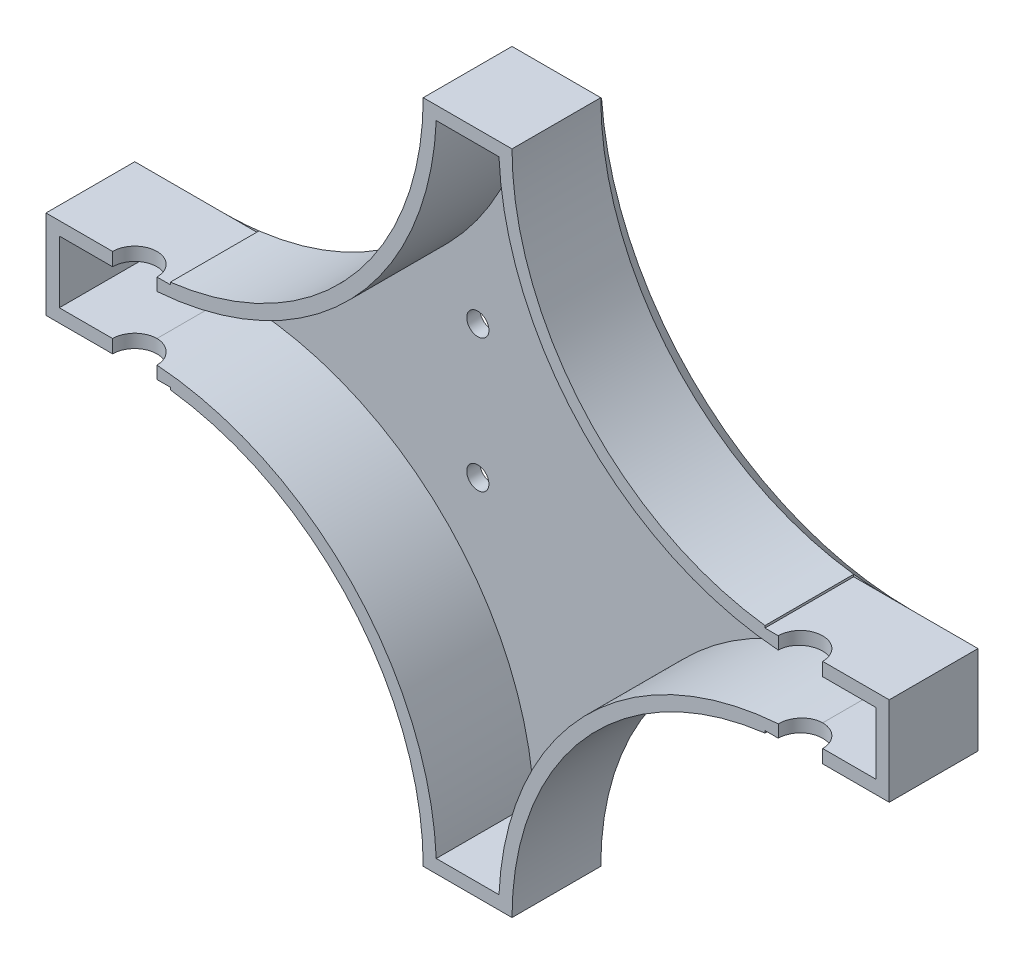
SolidWorks part; units mm, degrees
ref_plane "Front Plane" through (0, 0, 0) normal (0, 0, 1) x (1, 0, 0)
ref_plane "Top Plane" through (0, 0, 0) normal (0, 1, 0) x (1, 0, 0)
ref_plane "Right Plane" through (0, 0, 0) normal (1, 0, 0) x (0, 0, -1)
sketch "Sketch1" plane through (0, 0, 0) normal (0, 0, 1) x (1, 0, 0)
  line L1 (100, -75) -> (-100, -75)
  line L2 (100, -75) -> (100, 75)
  line L3 (100, 75) -> (-100, 75)
  line L4 (-100, -75) -> (-100, 75)
  line L5 (100, -75) -> (-100, 75) construction
  line L6 (100, 75) -> (-100, -75) construction
  point P0 (0, 0)
  dimension "D1" = 150
  dimension "D2" = 200
extrude "Boss-Extrude1" add sketch "Sketch1" along normal blind 25
sketch "Sketch2" plane through (0, 0, 0) normal (0, 0, -1) x (-1, 0, 0)
  line L0 (-100, 0) -> (100, 0)
  line L1 (0, 112.9215) -> (0, -139.2829) construction
  line L4 (-100, -75) -> (-100, 75) construction
  line L5 (100, 75) -> (100, -75) construction
sketch "Sketch5" plane through (0, 0, 0) normal (0, 0, -1) x (-1, 0, 0)
  line L0 (-100, 10) -> (106.2721, 10)
  line L1 (-100, -75) -> (-100, 75) construction
  line L2 (-15, -75) -> (5, -75)
  line L3 (-15, 75) -> (-15, -75)
  line L4 (-100, 0) -> (100, 0)
  line L5 (0, 10) -> (0, -10)
  line L6 (-65, -10) -> (101.6807, -10)
  line L7 (-65, -10) -> (-100, -10)
  line L8 (100, 75) -> (100, -75) construction
  line L9 (-100, 75) -> (100, 75) construction
  line L10 (100, -75) -> (-100, -75) construction
  line L11 (0, 112.9215) -> (0, -139.2829) construction
  line L12 (-15, 75) -> (5, 75)
  arc A3 (-80, 10) -> (-15, 75) centre (-80, 75) ccw
  arc A4 (-80, -10) -> (-15, -75) centre (-80, -75) cw
  arc A5 (5, 75) -> (70, 10) centre (70, 75) ccw
  arc A6 (5, -75) -> (70, -10) centre (70, -75) cw
  point P32 (70, -75)
  point P35 (70, -75)
  line M4 (100, -75) -> (100, 75)
  line M5 (100, 75) -> (-100, 75)
  line M6 (-100, 75) -> (-100, -75)
  line M7 (-100, -75) -> (100, -75)
  dimension "D2" = 15
  dimension "D3" = 130
  dimension "D4" = 130
  dimension "D5" = 100
  dimension "D6" = 85
extrude "Cut-Extrude2" cut sketch "Sketch5" against normal blind 30 contours A5 L0 M5 M4 | A6 L6 M7 M4 | A4 L7 M6 M7 | L0 A3 M5 M6 region at (62.9934, 46.0302, 0) region at (62.9934, -46.0302, 0) region at (-58.1762, 45.5946, 0) region at (-58.1762, -45.5946, 0)
shell "Shell2" thickness 3 removed face at (3.3333, 0, 25)
sketch "Sketch6" plane through (0, 0, 0) normal (0, 0, -1) x (-1, 0, 0)
  line L0 (-15, 75) -> (5, 75) construction
  line L1 (5, -75) -> (-15, -75) construction
  circle A0 centre (-5, 65) radius 2.5
  circle A1 centre (-5, -65) radius 2.5
  dimension "D1" = 5
  dimension "D2" = 5
  dimension "D3" = 10
  dimension "D4" = 10
extrude "Cut-Extrude3" cut sketch "Sketch6" against normal blind 30
sketch "Sketch7" plane through (0, 0, 0) normal (0, 1, 0) x (1, 0, 0)
  line L0 (-70, -25) -> (-100, -25) construction
  circle A0 centre (-80, -25) radius 5
  circle A1 centre (80, -25) radius 5
  dimension "D1" = 10
  dimension "D2" = 10
  dimension "D3" = 20
  dimension "D4" = 20
extrude "Cut-Extrude4" cut sketch "Sketch7" against normal blind 30 and the other way blind 30
chamfer "Chamfer1" distance 5 angle 45 12 edges at (-24.0381, 29.0381, 0) (-85, 10, 0) (-100, 0, 0) (-85, -10, 0) (90, -10, 0) (-24.0381, -29.0381, 0) (5, -75, 0) (34.0381, -29.0381, 0) (100, 0, 0) (5, 75, 0) (34.0381, 29.0381, 0) (90, 10, 0)
sketch "Sketch8" plane through (0, 0, 3) normal (0, 0, 1) x (1, 0, 0)
  line L0 (-24.8165, 0) -> (36.3426, 0) construction
  circle A0 centre (-22, 15) radius 2.5
  circle A1 centre (-22, -15) radius 2.5
  dimension "D1" = 5
  dimension "D2" = 15
  dimension "D3" = 22
extrude "Cut-Extrude5" cut sketch "Sketch8" against normal blind 10
sketch "Sketch9" plane through (0, 0, 0) normal (0, 0, 1) x (1, 0, 0)
  line L0 (15, 75) -> (-5, 75) construction
  line L1 (-5, -75) -> (15, -75) construction
  line L2 (5, 75) -> (5, -75)
  line L3 (5, -75) -> (-100, -75)
  line L4 (-100, -75) -> (-100, 75)
  line L5 (-100, 75) -> (5, 75)
extrude "Cut-Extrude8" cut sketch "Sketch9" along normal blind 50
mirror "Mirror4" about plane through (5, 75, 50) normal (-1, 0, 0) of bodies 113
sketch "Sketch10" plane through (0, 0, 0) normal (0, 0, 1) x (1, 0, 0)
  line L1 (-87, -7) -> (-87, 7) construction
  circle A0 centre (-14.7, 15) radius 2.5
  circle A1 centre (-14.7, -15) radius 2.5
  dimension "D1" = 5
  dimension "D2" = 5
  dimension "D3" = 72.3
  dimension "D5" = 30
  dimension "D6" = 15
extrude "Cut-Extrude9" cut sketch "Sketch10" along normal blind 50
sketch "Sketch11" plane through (-90, 0, 0) normal (-1, 0, 0) x (0, 0, 1)
  line L0 (5, 10) -> (5, 75) construction
  line L1 (5, 12.691) -> (25, 12.691)
  line L2 (5, 12.691) -> (5, 10)
  line L3 (5, 10) -> (25, 10)
  line L4 (25, 12.691) -> (25, 10)
  line L6 (5, -10) -> (25.0204, -10)
  line L7 (5, -10) -> (5, -12.7712)
  line L8 (5, -12.7712) -> (25.0204, -12.7712)
  line L9 (25.0204, -10) -> (25.0204, -12.7712)
extrude "Cut-Extrude10" cut sketch "Sketch11" against normal blind 28
sketch "Sketch12" plane through (100, 0, 0) normal (1, 0, 0) x (0, 0, -1)
  line L0 (-5, 10) -> (-5, 75) construction
  line L1 (-25, 10) -> (-5, 10)
  line L2 (-25, 10) -> (-25, 13.9268)
  line L3 (-25, 13.9268) -> (-5, 13.9268)
  line L4 (-5, 10) -> (-5, 13.9268)
  line L5 (-5, -75) -> (-5, -10) construction
  line L6 (-25, -10) -> (-5, -10)
  line L7 (-25, -10) -> (-25, -13.9268)
  line L8 (-25, -13.9268) -> (-5, -13.9268)
  line L9 (-5, -10) -> (-5, -13.9268)
extrude "Cut-Extrude11" cut sketch "Sketch12" against normal blind 28
sketch "草图1" plane through (0, 0, 3) normal (0, 0, 1) x (1, 0, 0)
  line L1 (-0.5, 12.6932) -> (24.5, 12.6932)
  line L2 (-0.5, 12.6932) -> (-0.5, -12.3068)
  line L3 (-0.5, -12.3068) -> (24.5, -12.3068)
  line L4 (24.5, 12.6932) -> (24.5, -12.3068)
  line L5 (-0.5, 12.6932) -> (24.5, -12.3068) construction
  line L6 (-0.5, -12.3068) -> (24.5, 12.6932) construction
  point P0 (12, 0.1932)
  dimension "D1" = 25
  dimension "D2" = 25
  dimension "D3" = 12
extrude "凸台-拉伸1" add sketch "草图1" against normal blind 5
chamfer "倒角1" distance 2 angle 45 4 edges at (12, 12.6932, -2) (-0.5, 0.1932, -2) (12, -12.3068, -2) (24.5, 0.1932, -2)
sketch "草图2" plane through (0, 0, -2) normal (0, 0, -1) x (-1, 0, 0)
  line L1 (-22.5, 10.6932) -> (-22.5, -10.3068) construction
  line L2 (-1.5, -10.3068) -> (-1.5, 10.6932) construction
  line L3 (-1.5, 10.6932) -> (-22.5, 10.6932) construction
  line L4 (-22.5, -10.3068) -> (-1.5, -10.3068) construction
  circle A0 centre (-17, 5.6932) radius 4
  circle A1 centre (-7, 5.6932) radius 4
  circle A2 centre (-17, -5.3068) radius 4
  circle A3 centre (-7, -5.3068) radius 4
  dimension "D1" = 8
  dimension "D2" = 8
  dimension "D3" = 8
  dimension "D4" = 8
  dimension "D5" = 5.5
  dimension "D6" = 5.5
  dimension "D7" = 5.5
  dimension "D8" = 5.5
  dimension "D9" = 5
  dimension "D10" = 5
  dimension "D11" = 5
  dimension "D12" = 5
extrude "凸台-拉伸2" add sketch "草图2" along normal blind 5
chamfer "倒角4" distance 1 angle 45 4 edges at (3, -5.3068, -7) (3, 5.6932, -7) (13, 5.6932, -7) (13, -5.3068, -7)
